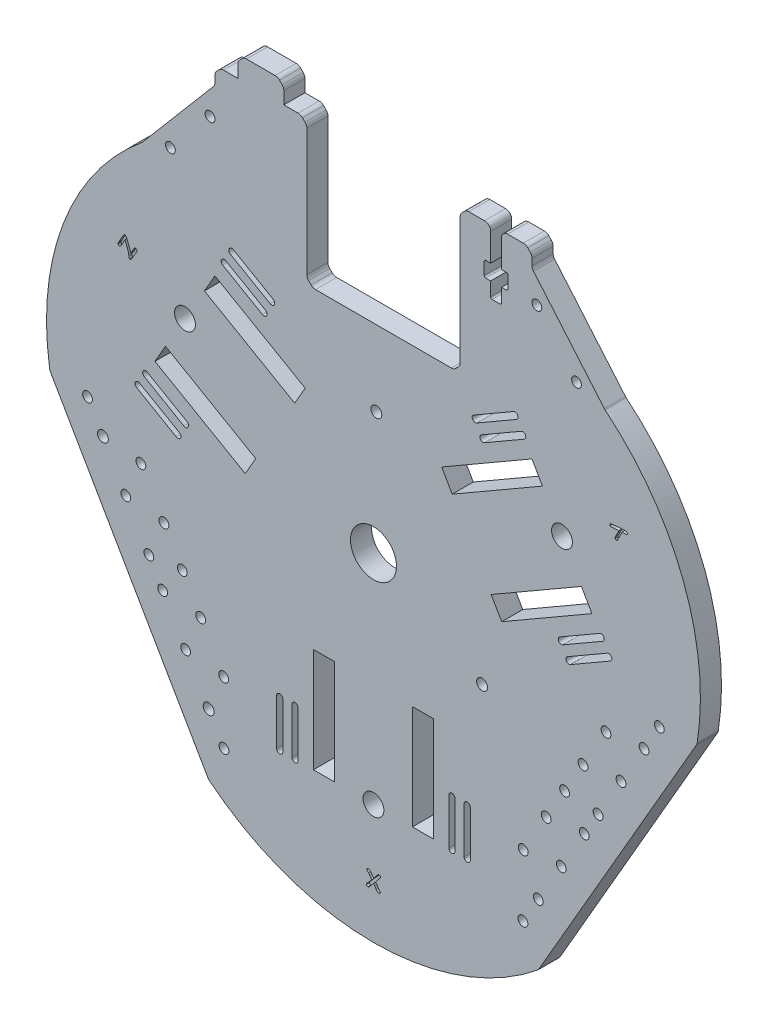
SolidWorks part; units mm, degrees
ref_plane "Front Plane" through (0, 0, 0) normal (0, 0, 1) x (1, 0, 0)
ref_plane "Top Plane" through (0, 0, 0) normal (0, 1, 0) x (1, 0, 0)
ref_plane "Right Plane" through (0, 0, 0) normal (1, 0, 0) x (0, 0, -1)
sketch "Sketch1" plane through (0, 0, 0) normal (0, 0, 1) x (1, 0, 0)
  circle A0 centre (0, 0) radius 110
  dimension "D1" = 220
extrude "Boss-Extrude1" add sketch "Sketch1" along normal blind 6.88
sketch "Sketch2" plane through (0, 0, 6.88) normal (0, 0, 1) x (1, 0, 0)
  line L0 (-105.5392, -1.2008) -> (-53.8095, -90.7992)
  line L1 (53.8095, -90.7992) -> (105.5392, -1.2008)
  line L2 (51.7297, 92) -> (-51.7297, 92)
  line L3 (-21.6506, 12.5) -> (21.6506, 12.5)
  line L4 (21.6506, 12.5) -> (0, -25)
  line L5 (0, -25) -> (-21.6506, 12.5)
  line L6 (0, 12.5) -> (0, 0) construction
  line L7 (0, 0) -> (-10.8253, -6.25) construction
  line L8 (10.8253, -6.25) -> (0, 0) construction
  arc A0 (-53.8095, -90.7992) -> (53.8095, -90.7992) centre (0, -25) ccw
  arc A1 (105.5392, -1.2008) -> (51.7297, 92) centre (21.6506, 12.5) ccw
  arc A2 (-51.7297, 92) -> (-105.5392, -1.2008) centre (-21.6506, 12.5) ccw
  circle A3 centre (0, 0) radius 250
  circle A4 centre (0, 0) radius 110
  circle M1 centre (0, 0) radius 110
  dimension "D3" = 220
  dimension "D4" = 500
  dimension "D5" = 85
  dimension "D1" = 92
extrude "Cut-Extrude1" cut sketch "Sketch2" against normal through all contours A3 M1 | A2 L2 A1 M1 | A2 A0 L0 M1 | A1 L1 A0 M1 region at (-84.8334, -48.9786, 6.88) region at (0, 97.9571, 6.88) region at (84.8334, -48.9786, 6.88) region at (-242.9289, 0, 6.88)
sketch "Sketch3" plane through (0, 0, 6.88) normal (0, 0, 1) x (1, 0, 0)
  line L0 (0, 0) -> (-95.2628, 55) construction
  line L1 (0, 0) -> (95.2628, 55) construction
  line L2 (0, 0) -> (0, -110) construction
  arc A0 (-51.7297, 92) -> (-105.5392, -1.2008) centre (-21.6506, 12.5) ccw construction
  arc A1 (105.5392, -1.2008) -> (51.7297, 92) centre (21.6506, 12.5) ccw construction
  arc A2 (-53.8095, -90.7992) -> (53.8095, -90.7992) centre (0, -25) ccw construction
sketch "Sketch4" plane through (0, 0, 0) normal (0, 0, -1) x (-1, 0, 0)
  line L4 (41.8329, 1.5432) -> (38.3929, 7.5015)
  line L5 (25.6929, 29.4985) -> (22.2529, 35.4568)
  line L6 (55.1378, 46.4985) -> (51.6978, 52.4568)
  line L7 (71.2778, 18.5432) -> (67.8378, 24.5015)
  line L8 (71.2778, 18.5432) -> (41.8329, 1.5432)
  line L9 (38.3929, 7.5015) -> (67.8378, 24.5015)
  line L10 (55.1378, 46.4985) -> (25.6929, 29.4985)
  line L11 (22.2529, 35.4568) -> (51.6978, 52.4568)
  line L12 (67.8378, 24.5015) -> (55.1378, 46.4985) construction
  line L13 (38.3929, 7.5015) -> (25.6929, 29.4985) construction
  line L14 (61.4878, 35.5) -> (32.0429, 18.5) construction
  circle A0 centre (32.0429, 18.5) radius 3.4 construction
  circle A1 centre (61.4878, 35.5) radius 3.4
  dimension "D1" = 6.8
extrude "Cut-Extrude2" cut sketch "Sketch4" against normal blind 10
ref_axis "Axis1" through (0, 0, -0.344) along (0, 0, 1)
pattern_circular "CirPattern1" count 3 over 360 about axis through (0, 0, -0.344) along (0, 0, 1) of "Cut-Extrude2"
sketch "Sketch6" plane through (0, 0, 6.88) normal (0, 0, 1) x (1, 0, 0)
  line L0 (-21.7297, 112) -> (-21.7297, 97)
  line L1 (51.7297, 92) -> (-51.7297, 92)
  line L2 (51.7297, 92) -> (51.7297, 112)
  line L3 (51.7297, 112) -> (28.2703, 112)
  line L4 (-51.7297, 92) -> (-51.7297, 112)
  line L5 (-21.7297, 97) -> (28.2703, 97)
  line L6 (28.2703, 97) -> (28.2703, 112)
  line L7 (-21.7297, 112) -> (-51.7297, 112)
  dimension "D1" = 20
  dimension "D2" = 15
  dimension "D3" = 50
  dimension "D4" = 30
extrude "Boss-Extrude2" add sketch "Sketch6" against normal up to vertex (6.88 mm away) up to point (51.7297, 92, 0)
chamfer "Chamfer1" distance 21 angle 45 2 edges at (-51.7297, 92, 3.44) (51.7297, 92, 3.44) first distance on face at (-51.7297, 102, 3.44) first distance on face at (51.7297, 102, 3.44)
sketch "Sketch7" plane through (0, 0, 6.88) normal (0, 0, 1) x (1, 0, 0)
  line L0 (-21.7297, 112) -> (-51.7297, 112) construction
  line L1 (-21.7297, 97) -> (28.2703, 97)
  line L2 (-21.7297, 97) -> (-21.7297, 65)
  line L3 (-21.7297, 65) -> (28.2703, 65)
  line L4 (28.2703, 97) -> (28.2703, 65)
  line L5 (28.2703, 112) -> (28.2703, 97) construction
  dimension "D1" = 47
extrude "Cut-Extrude5" cut sketch "Sketch7" against normal through all
sketch "Sketch8" plane through (0, 0, 6.88) normal (0, 0, 1) x (1, 0, 0)
  line L0 (51.7297, 112) -> (28.2703, 112) construction
  line L5 (41.775, 133) -> (38.225, 133)
  line L6 (41.775, 133) -> (41.775, 91)
  line L7 (41.775, 91) -> (38.225, 91)
  line L8 (38.225, 133) -> (38.225, 91)
  line L9 (41.775, 133) -> (38.225, 91) construction
  line L10 (41.775, 91) -> (38.225, 133) construction
  line L12 (43.86, 96) -> (36.14, 96)
  line L13 (43.86, 96) -> (43.86, 101)
  line L14 (43.86, 101) -> (36.14, 101)
  line L15 (36.14, 96) -> (36.14, 101)
  line L16 (43.86, 96) -> (36.14, 101) construction
  line L17 (43.86, 101) -> (36.14, 96) construction
  point P0 (40, 112)
  point P7 (40, 98.5)
  line M13 (51.7297, 112) -> (28.2703, 112)
  dimension "D1" = 3.55
  dimension "D2" = 21
  dimension "D3" = 7.72
  dimension "D4" = 5
  dimension "D5" = 11
extrude "Cut-Extrude6" cut sketch "Sketch8" against normal blind 6.88 contours L13 L14 L6 L12 | L6 L12 L8 L7 | L6 L14 L8 L12 | L15 L12 L8 L14 | L14 L6 L8 M13 region at (40, 106.5, 6.88) region at (42.8175, 98.5, 6.88) region at (40, 98.5, 6.88) region at (37.1825, 98.5, 6.88) region at (40, 93.5, 6.88)
sketch "Sketch9" plane through (0, 0, 6.88) normal (0, 0, 1) x (1, 0, 0)
  line L0 (-21.7297, 112) -> (-51.7297, 112) construction
  line L1 (-29.2297, 105.12) -> (-44.2297, 105.12)
  line L2 (-29.2297, 105.12) -> (-29.2297, 118.88)
  line L3 (-29.2297, 118.88) -> (-44.2297, 118.88)
  line L4 (-44.2297, 105.12) -> (-44.2297, 118.88)
  line L5 (-29.2297, 105.12) -> (-44.2297, 118.88) construction
  line L6 (-29.2297, 118.88) -> (-44.2297, 105.12) construction
  point P0 (-36.7297, 112)
  dimension "D1" = 15
  dimension "D2" = 6.88
extrude "Boss-Extrude3" add sketch "Sketch9" against normal up to vertex (6.88 mm away) up to point (-21.7297, 112, 0)
sketch "Sketch10" plane through (0, 0, 6.88) normal (0, 0, 1) x (1, 0, 0)
  line L4 (25.58, -71) -> (25.58, -56) construction
  line L5 (24.58, -71) -> (24.58, -56)
  line L6 (26.58, -71) -> (26.58, -56)
  line L7 (25.58, -63.5) -> (30.58, -63.5) construction
  line L8 (28.08, -63.5) -> (28.08, -58.2067) construction
  line L9 (19.58, -71) -> (19.58, -37) construction
  line L10 (30.58, -71) -> (30.58, -56) construction
  line L11 (31.58, -71) -> (31.58, -56)
  line L12 (29.58, -71) -> (29.58, -56)
  line L15 (-25.58, -71) -> (-25.58, -56) construction
  line L16 (-24.58, -71) -> (-24.58, -56)
  line L17 (-26.58, -71) -> (-26.58, -56)
  line L18 (-30.58, -71) -> (-30.58, -56) construction
  line L19 (-31.58, -71) -> (-31.58, -56)
  line L20 (-29.58, -71) -> (-29.58, -56)
  line L21 (-28.08, -63.5) -> (-28.08, -58.2067) construction
  line L22 (-25.58, -63.5) -> (-30.58, -63.5) construction
  arc A0 (24.58, -71) -> (26.58, -71) centre (25.58, -71) ccw
  arc A1 (26.58, -56) -> (24.58, -56) centre (25.58, -56) ccw
  arc A2 (31.58, -71) -> (29.58, -71) centre (30.58, -71) cw
  arc A3 (29.58, -56) -> (31.58, -56) centre (30.58, -56) cw
  arc A4 (-24.58, -71) -> (-26.58, -71) centre (-25.58, -71) cw
  arc A5 (-26.58, -56) -> (-24.58, -56) centre (-25.58, -56) cw
  arc A6 (-31.58, -71) -> (-29.58, -71) centre (-30.58, -71) ccw
  arc A7 (-29.58, -56) -> (-31.58, -56) centre (-30.58, -56) ccw
  point P0 (0, 0)
  point P6 (25.58, -63.5)
  point P21 (30.58, -63.5)
  point P30 (-25.58, -63.5)
  point P37 (-30.58, -63.5)
  dimension "D1" = 2
  dimension "D2" = 15
  dimension "D3" = 5
  dimension "D4" = 1.5
extrude "Cut-Extrude7" cut sketch "Sketch10" against normal blind 6.88
pattern_circular "CirPattern2" count 3 over 360 about axis through (0, 0, -0.344) along (0, 0, 1) of "Cut-Extrude7"
sketch "Sketch11" plane through (0, 0, 0) normal (0, 0, -1) x (-1, 0, 0)
  line L0 (-0.9365, 40.3779) -> (-35.4365, -19.3779) construction
  line L1 (-35.4365, -19.3779) -> (53.7641, -70.8779) construction
  line L2 (53.7641, -70.8779) -> (88.2641, -11.1221) construction
  line L3 (88.2641, -11.1221) -> (-0.9365, 40.3779) construction
  line L4 (71.0141, -41) -> (79.6743, -46) construction
  line L5 (105.5392, -1.2008) -> (53.8095, -90.7992) construction
  circle A4 centre (-0.9365, 40.3779) radius 1.775
  circle A5 centre (-35.4365, -19.3779) radius 1.775
  circle A6 centre (88.2641, -11.1221) radius 1.775
  circle A7 centre (53.7641, -70.8779) radius 1.775
  dimension "D4" = 3.55
  dimension "D1" = 69
  dimension "D2" = 103
  dimension "D3" = 10
extrude "Cut-Extrude8" cut sketch "Sketch11" against normal blind 10
chamfer "Chamfer2" distance 2 angle 45 8 edges at (28.2703, 65, 3.44) (-21.7297, 65, 3.44) (28.2703, 112, 3.44) (51.7297, 112, 3.44) (-51.7297, 112, 3.44) (-44.2297, 118.88, 3.44) (-29.2297, 118.88, 3.44) (-21.7297, 112, 3.44)
sketch "Sketch13" plane through (0, 0, 0) normal (0, 0, -1) x (-1, 0, 0)
  circle A0 centre (0, 0) radius 7.5
  dimension "D1" = 15
extrude "Cut-Extrude10" cut sketch "Sketch13" against normal blind 10
sketch "Sketch15" plane through (0, 0, 0) normal (0, 0, -1) x (-1, 0, 0)
  line L1 (0, 0) -> (0, -110) construction
  line L2 (-34.5, 82) -> (-19.5, 82) construction
  line L3 (-27, 82) -> (-27, 72) construction
  line L4 (0, 92) -> (0, 117.1571) construction
  line L5 (27, 82) -> (27, 72) construction
  line L6 (34.5, 82) -> (19.5, 82) construction
  line L7 (-34.5, 82) -> (-44.5, 82) construction
  circle A0 centre (-34.5, 82) radius 1.6 construction
  circle A1 centre (-27, 72) radius 1.6 construction
  circle A2 centre (-19.5, 82) radius 1.6 construction
  circle A3 centre (-4.5, 82) radius 1.6 construction
  circle A4 centre (-12, 72) radius 1.6 construction
  circle A5 centre (0, 82) radius 1.6 construction
  circle A6 centre (0, 72) radius 1.6 construction
  circle A7 centre (12, 72) radius 1.6 construction
  circle A8 centre (4.5, 82) radius 1.6 construction
  circle A9 centre (19.5, 82) radius 1.6 construction
  circle A10 centre (27, 72) radius 1.6 construction
  circle A11 centre (34.5, 82) radius 1.6 construction
  circle A34 centre (53.7641, -70.8779) radius 1.6
  circle A35 centre (48.8538, -59.3827) radius 1.6
  circle A36 centre (61.2641, -57.8875) radius 1.6
  circle A37 centre (56.3538, -46.3923) radius 1.6
  circle A38 centre (68.7641, -44.8971) radius 1.6
  circle A39 centre (62.3538, -36) radius 1.6
  circle A40 centre (73.2641, -37.1029) radius 1.6
  circle A41 centre (68.3538, -25.6077) radius 1.6
  circle A42 centre (80.7641, -24.1125) radius 1.6
  circle A43 centre (75.8538, -12.6173) radius 1.6
  circle A44 centre (88.2641, -11.1221) radius 1.6
  circle A45 centre (-88.2641, -11.1221) radius 1.6
  circle A46 centre (-75.8538, -12.6173) radius 1.6
  circle A47 centre (-80.7641, -24.1125) radius 1.6
  circle A48 centre (-68.3538, -25.6077) radius 1.6
  circle A49 centre (-73.2641, -37.1029) radius 1.6
  circle A50 centre (-62.3538, -36) radius 1.6
  circle A51 centre (-68.7641, -44.8971) radius 1.6
  circle A52 centre (-56.3538, -46.3923) radius 1.6
  circle A53 centre (-61.2641, -57.8875) radius 1.6
  circle A54 centre (-48.8538, -59.3827) radius 1.6
  circle A55 centre (-53.7641, -70.8779) radius 1.6
  circle A56 centre (-44.5, 82) radius 1.6 construction
  circle A57 centre (44.5, 82) radius 1.6 construction
  circle A58 centre (93.2641, -2.4619) radius 1.6
  circle A59 centre (48.7641, -79.5381) radius 1.6
  circle A60 centre (-48.7641, -79.5381) radius 1.6
  circle A61 centre (-93.2641, -2.4619) radius 1.6
  point P78 (0, 0)
  point P80 (0, 0)
  point P92 (0, 0)
  dimension "D2" = 3.2
  dimension "D1" = 82
  dimension "D3" = 34.5
  dimension "D4" = 15
  dimension "D5" = 10
  dimension "D6" = 15
  dimension "D7" = 15
  dimension "D8" = 3
  dimension "D9" = 10
  dimension "D10" = 3
extrude "Cut-Extrude11" cut sketch "Sketch15" against normal blind 10
sketch "Sketch16" [suppressed] plane through (0, 0, 0) normal (0, 0, -1) x (-1, 0, 0)
  line L0 (0, 0) -> (-95.2628, 55) construction
  line L1 (0, 0) -> (-95.2628, 55) construction
  circle A0 centre (-48.7641, -79.5381) radius 1.6 construction
  circle A1 centre (-53.7641, -70.8779) radius 1.6 construction
  circle A2 centre (-68.7641, -44.8971) radius 1.6 construction
  circle A3 centre (-61.2641, -57.8875) radius 1.6 construction
  circle A4 centre (-48.8538, -59.3827) radius 1.6 construction
  circle A5 centre (-56.3538, -46.3923) radius 1.6 construction
  circle A6 centre (-73.2641, -37.1029) radius 1.6 construction
  circle A7 centre (-62.3538, -36) radius 1.6 construction
  circle A8 centre (-68.3538, -25.6077) radius 1.6 construction
  circle A9 centre (-80.7641, -24.1125) radius 1.6 construction
  circle A10 centre (-75.8538, -12.6173) radius 1.6 construction
  circle A11 centre (-88.2641, -11.1221) radius 1.6 construction
  circle A12 centre (-93.2641, -2.4619) radius 1.6 construction
  circle A13 centre (-48.7641, -79.5381) radius 1.6 construction
  circle A14 centre (-53.7641, -70.8779) radius 1.6 construction
  circle A15 centre (-68.7641, -44.8971) radius 1.6 construction
  circle A16 centre (-61.2641, -57.8875) radius 1.6 construction
  circle A17 centre (-48.8538, -59.3827) radius 1.6 construction
  circle A18 centre (-56.3538, -46.3923) radius 1.6 construction
  circle A19 centre (-73.2641, -37.1029) radius 1.6 construction
  circle A20 centre (-62.3538, -36) radius 1.6 construction
  circle A21 centre (-68.3538, -25.6077) radius 1.6 construction
  circle A22 centre (-80.7641, -24.1125) radius 1.6 construction
  circle A23 centre (-75.8538, -12.6173) radius 1.6 construction
  circle A24 centre (-88.2641, -11.1221) radius 1.6 construction
  circle A25 centre (-93.2641, -2.4619) radius 1.6 construction
  circle A26 centre (-44.5, 82) radius 1.6
  circle A27 centre (-34.5, 82) radius 1.6
  circle A28 centre (-27, 72) radius 1.6
  circle A29 centre (-19.5, 82) radius 1.6
  circle A30 centre (-12, 72) radius 1.6
  circle A31 centre (0, 72) radius 1.6
  circle A32 centre (-4.5, 82) radius 1.6
  circle A33 centre (12, 72) radius 1.6
  circle A34 centre (27, 72) radius 1.6
  circle A35 centre (19.5, 82) radius 1.6
  circle A36 centre (4.5, 82) radius 1.6
  circle A37 centre (34.5, 82) radius 1.6
  circle A38 centre (44.5, 82) radius 1.6
extrude "Cut-Extrude12" [suppressed] cut sketch "Sketch16" against normal through all
sketch "Sketch17" plane through (0, 0, 0) normal (0, 0, -1) x (-1, 0, 0)
  line L0 (-53.3032, 96.6968) -> (-66.2356, 81.4405) construction
  line L2 (-51.7297, 106.2855) -> (-75.4371, 78.318) construction
  line L3 (-63.5834, 92.3018) -> (-59.7694, 89.0687) construction
  line L4 (0, 0) -> (0, 141.0352) construction
  line L5 (63.5834, 92.3018) -> (59.7694, 89.0687) construction
  line L6 (53.3032, 96.6968) -> (66.2356, 81.4405) construction
  circle A0 centre (-53.3032, 96.6968) radius 1.6
  circle A1 centre (-66.2356, 81.4405) radius 1.6
  circle A2 centre (66.2356, 81.4405) radius 1.6
  circle A3 centre (53.3032, 96.6968) radius 1.6
  dimension "D1" = 3.2
  dimension "D2" = 5
  dimension "D3" = 20
extrude "Cut-Extrude13" cut sketch "Sketch17" against normal through all
fillet "Fillet1" radius 2 26 edges at (28.2703, 67, 3.44) (26.2703, 65, 3.44) (-19.7297, 65, 3.44) (-21.7297, 67, 3.44) (-21.7297, 110, 3.44) (-23.7297, 112, 3.44) (-29.2297, 116.88, 3.44) (-31.2297, 118.88, 3.44) (-42.2297, 118.88, 3.44) (-44.2297, 116.88, 3.44) (-49.7297, 112, 3.44) (-51.7297, 110, 3.44) (-51.7297, 106.2855, 3.44) (-75.4371, 78.318, 3.44) (-105.5392, -1.2008, 3.44) (-53.8095, -90.7992, 3.44) (53.8095, -90.7992, 3.44) (105.5392, -1.2008, 3.44) (75.4371, 78.318, 3.44) (51.7297, 106.2855, 3.44) (51.7297, 110, 3.44) (49.7297, 112, 3.44) (41.775, 112, 3.44) (38.225, 112, 3.44) (28.2703, 110, 3.44) (30.2703, 112, 3.44)
fillet "Fillet2" radius 0.5 6 edges at (43.86, 101, 3.44) (36.14, 101, 3.44) (36.14, 96, 3.44) (38.225, 91, 3.44) (41.775, 91, 3.44) (43.86, 96, 3.44)
fillet "Fillet3" [suppressed] radius 2
sketch "Sketch19" [suppressed] plane through (0, 0, 0) normal (0, 0, -1) x (-1, 0, 0)
  line L0 (-10.7271, -95) -> (10.7271, -95) construction
  line L1 (-76.9089, 56.7899) -> (-87.6359, 38.2101) construction
  line L2 (87.6359, 38.2101) -> (76.9089, 56.7899) construction
  text T0 "Y" font "Comic Sans MS" height 5
  text T1 "Z" font "Comic Sans MS" height 5
  text T2 "X" font "Comic Sans MS" height 5
  point P3 (0, -95)
  point P11 (0, 0)
  dimension "D1" = 95
  dimension "D2" = 3
extrude "Cut-Extrude14" [suppressed] cut sketch "Sketch19" against normal blind 1
sketch "Sketch21" plane through (0, 0, 6.88) normal (0, 0, 1) x (1, 0, 0)
  line L3 (-78.1724, 46.8713) -> (-78.8151, 45.7584)
  line L4 (-81.0771, 48.0019) -> (-81.0695, 47.9829)
  line L5 (79.0614, 44.4043) -> (78.8481, 43.9905)
  arc A1 (1.382, -93.535) -> (0.6994, -92.5726) centre (-1578.1837, -1213.1564) ccw
  spline S73 degree 3 poles (-79.8089, 43.9708) (-79.8053, 43.9303) (-79.7986, 43.8529) (-79.7812, 43.7429) (-79.7571, 43.645) (-79.7284, 43.5585) (-79.6925, 43.4841) (-79.6511, 43.4214) (-79.6042, 43.3692) (-79.5668, 43.3446) (-79.5484, 43.3326) knots 0 0 0 0 0.170363 0.326298 0.466843 0.593383 0.708405 0.812561 0.908171 1 1 1 1
  spline S74 degree 3 poles (-79.5484, 43.3326) (-79.5338, 43.3251) (-79.505, 43.3104) (-79.459, 43.2963) (-79.4118, 43.2921) (-79.3639, 43.2947) (-79.3152, 43.3066) (-79.2654, 43.3252) (-79.2144, 43.3523) (-79.1641, 43.3895) (-79.1105, 43.4319) (-79.058, 43.4843) (-79.0035, 43.5437) (-78.9481, 43.6114) (-78.8921, 43.6876) (-78.8342, 43.7711) (-78.7758, 43.8628) (-78.738, 43.9276) (-78.7185, 43.961) knots 0 0 0 0 0.043059 0.084833 0.125337 0.166838 0.21007 0.256255 0.306058 0.361127 0.420073 0.485345 0.55525 0.631872 0.714622 0.803304 0.898392 1 1 1 1
  spline S75 degree 3 poles (-78.7185, 43.961) (-78.7075, 43.98) (-78.6843, 44.0201) (-78.6475, 44.0837) (-78.6068, 44.1537) (-78.563, 44.2308) (-78.5144, 44.3142) (-78.4619, 44.4043) (-78.4064, 44.5017) (-78.3473, 44.6026) (-78.2892, 44.7045) (-78.2327, 44.8009) (-78.1812, 44.8916) (-78.1325, 44.9746) (-78.0888, 45.0518) (-78.048, 45.1217) (-78.0113, 45.1853) (-77.988, 45.2254) (-77.9771, 45.2444) knots 0 0 0 0 0.044313 0.093873 0.148679 0.208169 0.273468 0.344014 0.419243 0.500282 0.580757 0.656549 0.726532 0.791831 0.851321 0.906127 0.955687 1 1 1 1
  spline S76 degree 3 poles (-77.9771, 45.2444) (-77.956, 45.2803) (-77.9093, 45.3598) (-77.8258, 45.4867) (-77.7276, 45.6369) (-77.6151, 45.7998) (-77.5021, 45.9626) (-77.4046, 46.114) (-77.3211, 46.2416) (-77.2742, 46.3215) (-77.2531, 46.3573) knots 0 0 0 0 0.093963 0.208302 0.343095 0.499348 0.6556 0.79072 0.906037 1 1 1 1
  spline S77 degree 3 poles (-77.2531, 46.3573) (-77.2288, 46.4024) (-77.1832, 46.4869) (-77.1371, 46.6155) (-77.1159, 46.7355) (-77.1197, 46.8473) (-77.1501, 46.9502) (-77.2068, 47.0427) (-77.288, 47.1256) (-77.3557, 47.1683) (-77.3913, 47.1908) knots 0 0 0 0 0.15879 0.298372 0.422591 0.535205 0.643047 0.75197 0.869499 1 1 1 1
  spline S78 degree 3 poles (-77.3913, 47.1908) (-77.4266, 47.2094) (-77.4944, 47.245) (-77.6021, 47.274) (-77.7082, 47.2834) (-77.7759, 47.27) (-77.8096, 47.2634) knots 0 0 0 0 0.27412 0.526385 0.764224 1 1 1 1
  spline S79 degree 3 poles (-77.8096, 47.2634) (-77.8385, 47.2545) (-77.8952, 47.2372) (-77.9702, 47.1903) (-78.0361, 47.1306) (-78.068, 47.0804) (-78.0844, 47.0546) knots 0 0 0 0 0.254442 0.49927 0.74205 1 1 1 1
  spline S80 degree 3 poles (-78.0844, 47.0546) (-78.091, 47.042) (-78.1068, 47.0119) (-78.1278, 46.9625) (-78.1503, 46.9139) (-78.1659, 46.8839) (-78.1724, 46.8713) knots 0 0 0 0 0.209165 0.501373 0.790835 1 1 1 1
  spline S81 degree 3 poles (-78.8151, 45.7584) (-78.8262, 45.7384) (-78.8496, 45.696) (-78.8852, 45.6286) (-78.9238, 45.554) (-78.9638, 45.472) (-79.006, 45.383) (-79.0501, 45.2867) (-79.0969, 45.1835) (-79.1283, 45.1118) (-79.1444, 45.0749) knots 0 0 0 0 0.090662 0.191149 0.30148 0.42237 0.552088 0.690654 0.84089 1 1 1 1
  spline S82 degree 3 poles (-79.1444, 45.0749) (-79.1576, 45.1359) (-79.1846, 45.2601) (-79.233, 45.4493) (-79.2873, 45.6455) (-79.3489, 45.8484) (-79.4176, 46.058) (-79.4926, 46.2745) (-79.5747, 46.4981) (-79.6338, 46.6485) (-79.6639, 46.7251) knots 0 0 0 0 0.107962 0.220249 0.338157 0.460533 0.587439 0.720131 0.857452 1 1 1 1
  spline S83 degree 3 poles (-79.6639, 46.7251) (-79.7727, 46.9905) (-79.9902, 47.5214) (-80.2105, 48.0511) (-80.3207, 48.3161) knots 0 0 0 0 0.499833 1 1 1 1
  spline S84 degree 3 poles (-80.3207, 48.3161) (-80.3348, 48.3514) (-80.3616, 48.4183) (-80.3992, 48.5138) (-80.4351, 48.5976) (-80.4652, 48.6718) (-80.4919, 48.7351) (-80.5144, 48.7878) (-80.5329, 48.8299) (-80.5444, 48.8541) (-80.5494, 48.8645) knots 0 0 0 0 0.191878 0.364018 0.517813 0.652086 0.768237 0.864663 0.941371 1 1 1 1
  spline S85 degree 3 poles (-80.5494, 48.8645) (-80.5769, 48.9152) (-80.6286, 49.0104) (-80.7169, 49.1355) (-80.8086, 49.2358) (-80.8787, 49.2827) (-80.9116, 49.3047) knots 0 0 0 0 0.299162 0.562747 0.795012 1 1 1 1
  spline S86 degree 3 poles (-80.9116, 49.3047) (-80.9402, 49.3194) (-80.9957, 49.3477) (-81.0858, 49.3661) (-81.1761, 49.3612) (-81.2319, 49.3409) (-81.2605, 49.3305) knots 0 0 0 0 0.264296 0.512369 0.749653 1 1 1 1
  spline S87 degree 3 poles (-81.2605, 49.3305) (-81.2864, 49.3179) (-81.3385, 49.2925) (-81.4083, 49.2362) (-81.4713, 49.1662) (-81.5054, 49.1114) (-81.5231, 49.0831) knots 0 0 0 0 0.234031 0.473013 0.727326 1 1 1 1
  spline S88 degree 3 poles (-81.5231, 49.0831) (-81.5447, 49.0453) (-81.5906, 48.9653) (-81.6637, 48.8387) (-81.743, 48.698) (-81.8317, 48.5447) (-81.925, 48.3768) (-82.0279, 48.1963) (-82.1367, 48.0017) (-82.2515, 47.7983) (-82.3662, 47.595) (-82.4751, 47.4001) (-82.5783, 47.2196) (-82.6732, 47.0523) (-82.7604, 46.8981) (-82.8401, 46.7575) (-82.9132, 46.6308) (-82.959, 46.5508) (-82.9806, 46.5131) knots 0 0 0 0 0.044177 0.093617 0.148485 0.208171 0.273451 0.343546 0.419071 0.49986 0.580648 0.656173 0.72655 0.791664 0.851515 0.906383 0.955823 1 1 1 1
  spline S89 degree 3 poles (-82.9806, 46.5131) (-82.9896, 46.4978) (-83.0093, 46.464) (-83.0445, 46.4098) (-83.0843, 46.345) (-83.1307, 46.2748) (-83.1771, 46.2048) (-83.2187, 46.1408) (-83.2524, 46.0857) (-83.2723, 46.0518) (-83.2813, 46.0366) knots 0 0 0 0 0.094259 0.20833 0.343845 0.499228 0.65614 0.790863 0.905741 1 1 1 1
  spline S90 degree 3 poles (-83.2813, 46.0366) (-83.2952, 46.0091) (-83.3224, 45.9552) (-83.3458, 45.8686) (-83.3509, 45.7796) (-83.3412, 45.7215) (-83.3363, 45.6919) knots 0 0 0 0 0.257821 0.50614 0.74815 1 1 1 1
  spline S91 degree 3 poles (-83.3363, 45.6919) (-83.3266, 45.658) (-83.3074, 45.5908) (-83.248, 45.5014) (-83.168, 45.4237) (-83.1024, 45.3848) (-83.0681, 45.3645) knots 0 0 0 0 0.240755 0.47726 0.727467 1 1 1 1
  spline S92 degree 3 poles (-83.0681, 45.3645) (-83.0436, 45.3526) (-82.9961, 45.3297) (-82.9209, 45.3114) (-82.8468, 45.3062) (-82.7732, 45.3158) (-82.7003, 45.3391) (-82.6283, 45.3766) (-82.5577, 45.428) (-82.514, 45.4697) (-82.4911, 45.4916) knots 0 0 0 0 0.127143 0.24646 0.360517 0.473263 0.592046 0.717219 0.85197 1 1 1 1
  spline S93 degree 3 poles (-82.4911, 45.4916) (-82.4806, 45.503) (-82.4574, 45.5282) (-82.4228, 45.5722) (-82.3842, 45.6244) (-82.3425, 45.6853) (-82.2978, 45.7552) (-82.249, 45.8332) (-82.1956, 45.9194) (-82.1607, 45.9805) (-82.1425, 46.0124) knots 0 0 0 0 0.074325 0.163329 0.267209 0.384702 0.515924 0.663666 0.824515 1 1 1 1
  spline S94 degree 3 poles (-82.1425, 46.0124) (-82.1244, 46.044) (-82.0867, 46.1096) (-82.0287, 46.2121) (-81.968, 46.3233) (-81.9036, 46.4429) (-81.8349, 46.5706) (-81.7615, 46.7061) (-81.6858, 46.8503) (-81.6341, 46.949) (-81.6076, 46.9995) knots 0 0 0 0 0.097389 0.202138 0.314694 0.435803 0.565015 0.702331 0.847477 1 1 1 1
  spline S95 degree 3 poles (-81.6076, 46.9995) (-81.5744, 47.0629) (-81.5112, 47.1831) (-81.4219, 47.3547) (-81.3403, 47.5067) (-81.2698, 47.6417) (-81.2086, 47.7579) (-81.1561, 47.8556) (-81.1129, 47.9344) (-81.0879, 47.9815) (-81.0771, 48.0019) knots 0 0 0 0 0.189219 0.359327 0.511764 0.645542 0.762101 0.859099 0.938881 1 1 1 1
  spline S96 degree 3 poles (-81.0695, 47.9829) (-80.949, 47.6953) (-80.7083, 47.121) (-80.4689, 46.5462) (-80.3494, 46.2592) knots 0 0 0 0 0.500735 1 1 1 1
  spline S97 degree 3 poles (-80.3494, 46.2592) (-80.3133, 46.1686) (-80.2433, 45.9928) (-80.148, 45.7349) (-80.0637, 45.4915) (-79.9922, 45.2619) (-79.9332, 45.0466) (-79.8866, 44.8456) (-79.8497, 44.6591) (-79.8352, 44.5385) (-79.8282, 44.4808) knots 0 0 0 0 0.157419 0.305348 0.443858 0.573146 0.693349 0.80399 0.906234 1 1 1 1
  spline S98 degree 3 poles (-79.8282, 44.4808) (-79.8255, 44.4321) (-79.8202, 44.3391) (-79.8168, 44.2052) (-79.8111, 44.084) (-79.8096, 44.007) (-79.8089, 43.9708) knots 0 0 0 0 0.286488 0.547701 0.786908 1 1 1 1
  spline S99 degree 3 poles (77.8969, 47.0732) (77.8628, 47.0708) (77.798, 47.0663) (77.7064, 47.0561) (77.6249, 47.0479) (77.5541, 47.0364) (77.493, 47.027) (77.4429, 47.0141) (77.4026, 47.0023) (77.3806, 46.9914) (77.371, 46.9867) knots 0 0 0 0 0.191773 0.363531 0.516818 0.6503 0.765427 0.862924 0.940305 1 1 1 1
  spline S100 degree 3 poles (77.371, 46.9867) (77.3448, 46.97) (77.2935, 46.9373) (77.2343, 46.8685) (77.1896, 46.7898) (77.1749, 46.7311) (77.1674, 46.701) knots 0 0 0 0 0.256848 0.501136 0.743719 1 1 1 1
  spline S101 degree 3 poles (77.1674, 46.701) (77.1633, 46.6725) (77.1553, 46.6168) (77.1588, 46.5324) (77.1813, 46.4515) (77.2062, 46.4017) (77.2188, 46.3765) knots 0 0 0 0 0.256863 0.502288 0.748988 1 1 1 1
  spline S102 degree 3 poles (77.2188, 46.3765) (77.2314, 46.3566) (77.2558, 46.3181) (77.3005, 46.2678) (77.3508, 46.2274) (77.4062, 46.1957) (77.4673, 46.1749) (77.5333, 46.1624) (77.6047, 46.1588) (77.6535, 46.1638) (77.6787, 46.1664) knots 0 0 0 0 0.130588 0.252745 0.371397 0.487402 0.605097 0.727826 0.859507 1 1 1 1
  spline S103 degree 3 poles (77.6787, 46.1664) (77.7185, 46.1708) (77.7955, 46.1791) (77.9071, 46.1926) (78.0111, 46.2049) (78.1072, 46.2159) (78.1956, 46.2254) (78.2763, 46.2342) (78.3493, 46.2419) (78.3953, 46.2472) (78.4169, 46.2497) knots 0 0 0 0 0.16161 0.312816 0.454135 0.584375 0.703539 0.812816 0.912207 1 1 1 1
  spline S104 degree 3 poles (78.4169, 46.2497) (78.5068, 46.2574) (78.6806, 46.2725) (78.9324, 46.2929) (79.1668, 46.3123) (79.3841, 46.33) (79.5841, 46.3444) (79.7668, 46.3568) (79.9318, 46.3691) (80.0363, 46.3751) (80.0858, 46.3779) knots 0 0 0 0 0.161623 0.312666 0.452882 0.58304 0.703391 0.812398 0.911098 1 1 1 1
  spline S105 degree 3 poles (80.0858, 46.3779) (80.0717, 46.3433) (80.0426, 46.2719) (79.9958, 46.1619) (79.9417, 46.0466) (79.8833, 45.925) (79.8192, 45.7977) (79.7503, 45.6641) (79.6755, 45.5245) (79.6232, 45.4298) (79.5964, 45.3815) knots 0 0 0 0 0.100897 0.208208 0.322866 0.444717 0.572584 0.707694 0.850803 1 1 1 1
  spline S106 degree 3 poles (79.5964, 45.3815) (79.5757, 45.3434) (79.5357, 45.2698) (79.4764, 45.1638) (79.4225, 45.0639) (79.3712, 44.9717) (79.3255, 44.8852) (79.2812, 44.8073) (79.2429, 44.7354) (79.2066, 44.6715) (79.1763, 44.6135) (79.1481, 44.5631) (79.1249, 44.5192) (79.1042, 44.483) (79.088, 44.4534) (79.0751, 44.4312) (79.0679, 44.4148) (79.0631, 44.4071) (79.0614, 44.4043) knots 0 0 0 0 0.116552 0.225678 0.327087 0.422258 0.509713 0.590481 0.663532 0.729156 0.788254 0.839923 0.884615 0.921881 0.952169 0.97548 0.991087 1 1 1 1
  spline S107 degree 3 poles (78.8481, 43.9905) (78.8342, 43.9485) (78.8079, 43.8693) (78.7952, 43.7494) (78.8094, 43.6373) (78.841, 43.5722) (78.8566, 43.5399) knots 0 0 0 0 0.284068 0.536293 0.770425 1 1 1 1
  spline S108 degree 3 poles (78.8566, 43.5399) (78.8727, 43.5149) (78.9047, 43.4656) (78.9668, 43.4034) (79.0396, 43.3538) (79.0942, 43.3322) (79.122, 43.3212) knots 0 0 0 0 0.253463 0.500454 0.74473 1 1 1 1
  spline S109 degree 3 poles (79.122, 43.3212) (79.1523, 43.3126) (79.2113, 43.2958) (79.3028, 43.294) (79.3913, 43.3128) (79.445, 43.3395) (79.4723, 43.353) knots 0 0 0 0 0.259642 0.5055 0.74858 1 1 1 1
  spline S110 degree 3 poles (79.4723, 43.353) (79.4893, 43.3636) (79.5231, 43.3845) (79.5675, 43.4258) (79.6071, 43.4728) (79.6286, 43.5084) (79.6395, 43.5264) knots 0 0 0 0 0.245834 0.488754 0.741621 1 1 1 1
  spline S111 degree 3 poles (79.6395, 43.5264) (79.6875, 43.6194) (79.7802, 43.7994) (79.9154, 44.0603) (80.0407, 44.3034) (80.155, 44.5296) (80.2622, 44.7366) (80.3579, 44.9269) (80.4446, 45.0993) (80.4986, 45.2084) (80.5241, 45.26) knots 0 0 0 0 0.161383 0.312047 0.452944 0.582975 0.702702 0.81225 0.911348 1 1 1 1
  spline S112 degree 3 poles (80.5241, 45.26) (80.5562, 45.3234) (80.6184, 45.4462) (80.7077, 45.6245) (80.7904, 45.7909) (80.8673, 45.9448) (80.9365, 46.0875) (80.9992, 46.2183) (81.0549, 46.3373) (81.09, 46.4127) (81.1066, 46.4483) knots 0 0 0 0 0.161104 0.312097 0.451971 0.582345 0.702008 0.811572 0.91104 1 1 1 1
  spline S113 degree 3 poles (81.1066, 46.4483) (81.1621, 46.4479) (81.2698, 46.4472) (81.4264, 46.4477) (81.5735, 46.4485) (81.7111, 46.4507) (81.8391, 46.4518) (81.9573, 46.4551) (82.0658, 46.4593) (82.1651, 46.4626) (82.2544, 46.4677) (82.3343, 46.4733) (82.4046, 46.4794) (82.4652, 46.4868) (82.5164, 46.4931) (82.5577, 46.5016) (82.5899, 46.5102) (82.6072, 46.5181) (82.6146, 46.5215) knots 0 0 0 0 0.109926 0.213525 0.31025 0.401525 0.486241 0.563782 0.635888 0.701435 0.760699 0.813128 0.860162 0.9004 0.934119 0.962325 0.983958 1 1 1 1
  spline S114 degree 3 poles (82.6146, 46.5215) (82.6404, 46.5384) (82.6913, 46.5718) (82.7508, 46.6414) (82.7951, 46.7228) (82.8098, 46.7833) (82.8174, 46.8145) knots 0 0 0 0 0.2506 0.494505 0.738383 1 1 1 1
  spline S115 degree 3 poles (82.8174, 46.8145) (82.8212, 46.8439) (82.8288, 46.9019) (82.8204, 46.989) (82.7986, 47.0739) (82.7718, 47.1259) (82.7582, 47.1524) knots 0 0 0 0 0.253219 0.499914 0.745374 1 1 1 1
  spline S116 degree 3 poles (82.7582, 47.1524) (82.7468, 47.1699) (82.7239, 47.2051) (82.6823, 47.2527) (82.6324, 47.2931) (82.576, 47.327) (82.5131, 47.3549) (82.4442, 47.378) (82.3678, 47.3927) (82.3146, 47.3985) (82.287, 47.4015) knots 0 0 0 0 0.113198 0.226596 0.339794 0.458695 0.580613 0.710968 0.849976 1 1 1 1
  spline S117 degree 3 poles (82.287, 47.4015) (82.2828, 47.4017) (82.272, 47.4023) (82.252, 47.4015) (82.2243, 47.4014) (82.1889, 47.4008) (82.1456, 47.4009) (82.0946, 47.3981) (82.0355, 47.3987) (81.9688, 47.396) (81.8943, 47.3947) (81.8118, 47.3914) (81.7216, 47.3894) (81.6233, 47.3861) (81.5173, 47.3841) (81.4034, 47.3807) (81.2819, 47.3759) (81.1984, 47.3739) (81.1552, 47.3729) knots 0 0 0 0 0.011108 0.02865 0.05306 0.084339 0.122486 0.167838 0.219722 0.278806 0.344758 0.417171 0.497605 0.583751 0.677918 0.778547 0.885639 1 1 1 1
  spline S118 degree 3 poles (81.1552, 47.3729) (81.1018, 47.3712) (80.9907, 47.3678) (80.8177, 47.3573) (80.6316, 47.3466) (80.4326, 47.3297) (80.2204, 47.3126) (79.9952, 47.2901) (79.7569, 47.2665) (79.5937, 47.2478) (79.51, 47.2383) knots 0 0 0 0 0.097209 0.201966 0.314821 0.435797 0.564886 0.701603 0.846975 1 1 1 1
  spline S119 degree 3 poles (79.51, 47.2383) (79.4116, 47.2274) (79.2237, 47.2067) (78.9554, 47.1778) (78.7137, 47.1516) (78.4986, 47.1303) (78.3103, 47.11) (78.1488, 47.095) (78.014, 47.0829) (77.933, 47.0762) (77.8969, 47.0732) knots 0 0 0 0 0.183229 0.349669 0.49932 0.632967 0.749583 0.849658 0.93295 1 1 1 1
  spline S120 degree 3 poles (2.1766, -90.6828) (2.1953, -90.6602) (2.2316, -90.6164) (2.2688, -90.5423) (2.2947, -90.4671) (2.297, -90.4156) (2.2982, -90.3899) knots 0 0 0 0 0.270792 0.525038 0.763041 1 1 1 1
  spline S121 degree 3 poles (2.2982, -90.3899) (2.2967, -90.3602) (2.2938, -90.3014) (2.2642, -90.2177) (2.2198, -90.1397) (2.1571, -90.0713) (2.0833, -90.0136) (2.0013, -89.9704) (1.9124, -89.9449) (1.8512, -89.9415) (1.82, -89.9398) knots 0 0 0 0 0.122374 0.241597 0.362385 0.491245 0.621635 0.747563 0.871468 1 1 1 1
  spline S122 degree 3 poles (1.82, -89.9398) (1.7979, -89.9427) (1.7474, -89.9494) (1.6696, -89.9913) (1.5801, -90.0541) (1.4775, -90.141) (1.3632, -90.2528) (1.2365, -90.3889) (1.0965, -90.5491) (1.0013, -90.6659) (0.9508, -90.7279) knots 0 0 0 0 0.055767 0.127167 0.218852 0.331347 0.464739 0.621075 0.798838 1 1 1 1
  spline S123 degree 3 poles (0.9508, -90.7279) (0.8143, -90.91) (0.5413, -91.2744) (0.2672, -91.638) (0.1301, -91.8199) knots 0 0 0 0 0.499814 1 1 1 1
  spline S124 degree 3 poles (0.1301, -91.8199) (0.0343, -91.6971) (-0.1575, -91.4512) (-0.3583, -91.2125) (-0.4589, -91.0929) knots 0 0 0 0 0.499031 1 1 1 1
  spline S125 degree 3 poles (-0.4589, -91.0929) (-0.5001, -91.0381) (-0.5774, -90.9353) (-0.6862, -90.7922) (-0.7776, -90.6689) (-0.8549, -90.5615) (-0.9287, -90.464) (-1.0096, -90.3719) (-1.0975, -90.2781) (-1.162, -90.2187) (-1.1951, -90.1882) knots 0 0 0 0 0.17628 0.330141 0.461386 0.57012 0.670036 0.775086 0.884584 1 1 1 1
  spline S126 degree 3 poles (-1.1951, -90.1882) (-1.2184, -90.1686) (-1.2631, -90.1311) (-1.3291, -90.0793) (-1.3931, -90.0375) (-1.452, -90.0005) (-1.5092, -89.9746) (-1.5616, -89.9541) (-1.6112, -89.9414) (-1.6433, -89.9398) (-1.6585, -89.939) knots 0 0 0 0 0.170917 0.326742 0.469276 0.599046 0.715434 0.820335 0.914589 1 1 1 1
  spline S127 degree 3 poles (-1.6585, -89.939) (-1.6906, -89.9403) (-1.7531, -89.9429) (-1.8417, -89.9715) (-1.9227, -90.015) (-1.9914, -90.0771) (-2.0484, -90.1483) (-2.0909, -90.2255) (-2.1177, -90.3075) (-2.1204, -90.364) (-2.1218, -90.3925) knots 0 0 0 0 0.133364 0.260079 0.384989 0.515081 0.6435 0.764635 0.881521 1 1 1 1
  spline S128 degree 3 poles (-2.1218, -90.3925) (-2.1194, -90.4254) (-2.1146, -90.4913) (-2.0782, -90.5859) (-2.0186, -90.6729) (-1.9336, -90.7491) (-1.8372, -90.8314) (-1.7393, -90.9348) (-1.6353, -91.0545) (-1.5674, -91.1426) (-1.5317, -91.1889) knots 0 0 0 0 0.097176 0.194604 0.295723 0.406526 0.530761 0.671034 0.826998 1 1 1 1
  spline S129 degree 3 poles (-1.5317, -91.1889) (-1.5052, -91.2237) (-1.4555, -91.2893) (-1.3857, -91.3816) (-1.3251, -91.4604) (-1.2762, -91.5279) (-1.2339, -91.58) (-1.2029, -91.6209) (-1.1815, -91.6487) (-1.1702, -91.6626) (-1.1663, -91.6673) knots 0 0 0 0 0.217994 0.410155 0.576482 0.713602 0.825303 0.910953 0.969183 1 1 1 1
  spline S130 degree 3 poles (-1.1663, -91.6673) (-1.0488, -91.8068) (-0.8159, -92.0832) (-0.594, -92.3684) (-0.484, -92.5096) knots 0 0 0 0 0.504629 1 1 1 1
  spline S131 degree 3 poles (-0.484, -92.5096) (-0.5423, -92.5753) (-0.6558, -92.7032) (-0.822, -92.8888) (-0.9785, -93.0643) (-1.1264, -93.2287) (-1.2651, -93.3824) (-1.3958, -93.5244) (-1.5161, -93.6565) (-1.5938, -93.7407) (-1.631, -93.7811) knots 0 0 0 0 0.153715 0.299593 0.436565 0.565703 0.687007 0.799234 0.903801 1 1 1 1
  spline S132 degree 3 poles (-1.631, -93.7811) (-1.6627, -93.8149) (-1.724, -93.8805) (-1.8129, -93.9757) (-1.8967, -94.0633) (-1.973, -94.146) (-2.044, -94.2212) (-2.1089, -94.29) (-2.1682, -94.3517) (-2.205, -94.3912) (-2.2224, -94.4099) knots 0 0 0 0 0.161173 0.311751 0.452803 0.582513 0.702697 0.812285 0.91128 1 1 1 1
  spline S133 degree 3 poles (-2.2224, -94.4099) (-2.2398, -94.4315) (-2.2735, -94.4735) (-2.3096, -94.5445) (-2.3317, -94.619) (-2.3344, -94.6702) (-2.3358, -94.6958) knots 0 0 0 0 0.263952 0.512523 0.755614 1 1 1 1
  spline S134 degree 3 poles (-2.3358, -94.6958) (-2.3341, -94.7254) (-2.3308, -94.7845) (-2.2979, -94.8689) (-2.2448, -94.9456) (-2.1738, -95.0133) (-2.0906, -95.071) (-1.997, -95.112) (-1.8969, -95.1385) (-1.8272, -95.1411) (-1.7917, -95.1424) knots 0 0 0 0 0.113792 0.226907 0.343765 0.471312 0.603284 0.731984 0.863489 1 1 1 1
  spline S135 degree 3 poles (-1.7917, -95.1424) (-1.7564, -95.1408) (-1.6874, -95.1378) (-1.587, -95.1112) (-1.4932, -95.0677) (-1.4377, -95.0263) (-1.4098, -95.0054) knots 0 0 0 0 0.255362 0.499585 0.747471 1 1 1 1
  spline S136 degree 3 poles (-1.4098, -95.0054) (-1.3796, -94.9713) (-1.3212, -94.9052) (-1.2372, -94.8091) (-1.1593, -94.7191) (-1.0867, -94.6362) (-1.0202, -94.5594) (-0.961, -94.4877) (-0.907, -94.4235) (-0.8731, -94.3826) (-0.8572, -94.3633) knots 0 0 0 0 0.160939 0.31252 0.452223 0.582202 0.70283 0.81197 0.911383 1 1 1 1
  spline S137 degree 3 poles (-0.8572, -94.3633) (-0.8109, -94.3096) (-0.7204, -94.2044) (-0.5883, -94.0492) (-0.4635, -93.8997) (-0.343, -93.7584) (-0.2297, -93.6225) (-0.1225, -93.493) (-0.0216, -93.3697) (0.0438, -93.29) (0.0756, -93.2513) knots 0 0 0 0 0.146479 0.286877 0.421198 0.548991 0.670709 0.78698 0.896329 1 1 1 1
  spline S138 degree 3 poles (0.0756, -93.2513) (0.1142, -93.3103) (0.1865, -93.4207) (0.2861, -93.5752) (0.3721, -93.7052) (0.4227, -93.7848) (0.4455, -93.8206) knots 0 0 0 0 0.311556 0.583243 0.8123 1 1 1 1
  spline S139 degree 3 poles (0.4455, -93.8206) (0.4666, -93.8552) (0.5073, -93.922) (0.5663, -94.0189) (0.6223, -94.1083) (0.6712, -94.1934) (0.7186, -94.2699) (0.7602, -94.341) (0.7985, -94.4046) (0.8219, -94.4453) (0.8329, -94.4646) knots 0 0 0 0 0.16176 0.311972 0.453203 0.582838 0.703509 0.812609 0.911442 1 1 1 1
  spline S140 degree 3 poles (0.8329, -94.4646) (0.8706, -94.5238) (0.9422, -94.6363) (1.0545, -94.7891) (1.1644, -94.9181) (1.2705, -95.0255) (1.3759, -95.1077) (1.4776, -95.1688) (1.5782, -95.2067) (1.6455, -95.2117) (1.6777, -95.2141) knots 0 0 0 0 0.179942 0.341675 0.485865 0.614026 0.727893 0.827563 0.917583 1 1 1 1
  spline S141 degree 3 poles (1.6777, -95.2141) (1.7137, -95.2124) (1.7841, -95.2091) (1.8864, -95.1843) (1.9801, -95.1407) (2.065, -95.0837) (2.1348, -95.0133) (2.1887, -94.9361) (2.2201, -94.8505) (2.2241, -94.7913) (2.2261, -94.7616) knots 0 0 0 0 0.137223 0.268869 0.398299 0.529968 0.657074 0.774519 0.886859 1 1 1 1
  spline S142 degree 3 poles (2.2261, -94.7616) (2.2249, -94.7354) (2.2225, -94.6829) (2.1968, -94.6069) (2.1607, -94.5318) (2.1246, -94.4876) (2.1059, -94.4646) knots 0 0 0 0 0.240035 0.478855 0.729825 1 1 1 1
  spline S143 degree 3 poles (2.1059, -94.4646) (2.05, -94.3998) (1.9327, -94.2637) (1.7573, -94.0427) (1.5713, -93.7981) (1.4468, -93.625) (1.382, -93.535) knots 0 0 0 0 0.217954 0.457158 0.717793 1 1 1 1
  spline S144 degree 3 poles (0.6994, -92.5726) (0.7441, -92.5161) (0.8303, -92.4068) (0.9545, -92.2479) (1.0705, -92.1008) (1.1736, -91.9614) (1.2716, -91.8355) (1.3568, -91.7175) (1.4336, -91.6111) (1.4811, -91.5434) (1.5034, -91.5114) knots 0 0 0 0 0.162217 0.313674 0.454371 0.584199 0.70433 0.81362 0.912174 1 1 1 1
  spline S145 degree 3 poles (1.5034, -91.5114) (1.5244, -91.4829) (1.5678, -91.424) (1.6362, -91.333) (1.7102, -91.2367) (1.7922, -91.1362) (1.8798, -91.0304) (1.9724, -90.9183) (2.0721, -90.802) (2.1412, -90.7232) (2.1766, -90.6828) knots 0 0 0 0 0.099494 0.205508 0.319718 0.440643 0.56981 0.705532 0.849205 1 1 1 1
extrude "Cut-Extrude15" cut sketch "Sketch21" against normal blind 1
